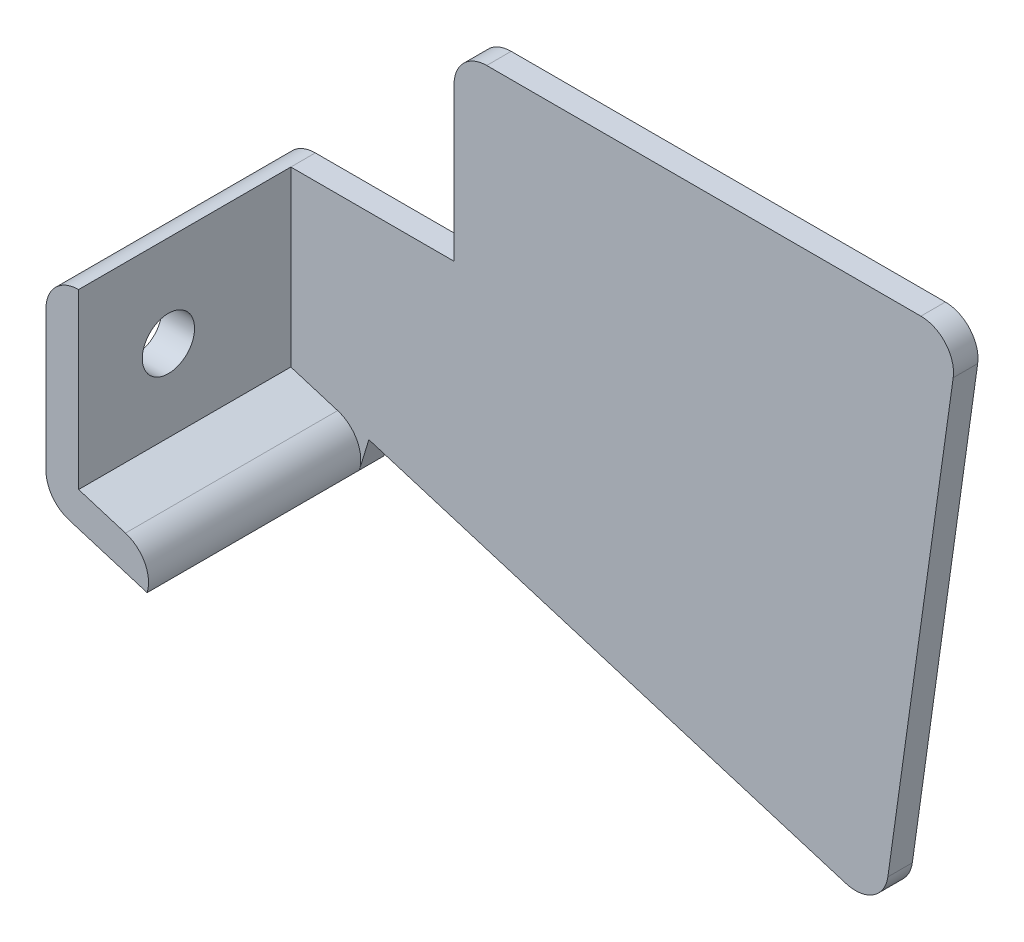
SolidWorks part; units mm, degrees
material "POLYURETHANE (11671)"
ref_plane "Front Plane" through (0, 0, 0) normal (0, 0, 1) x (1, 0, 0)
ref_plane "Top Plane" through (0, 0, 0) normal (0, 1, 0) x (1, 0, 0)
ref_plane "Right Plane" through (0, 0, 0) normal (1, 0, 0) x (0, 0, -1)
sketch "Sketch1" plane through (0, 0, 0) normal (0, 0, 1) x (1, 0, 0)
  line L5 (-6.1742, -3.4117) -> (24.7275, -3.4117)
  line L9 (20.078, -36.4952) -> (24.7275, -3.4117)
  line L16 (-18.1742, -24.8003) -> (20.078, -36.4952)
  line L17 (-18.1742, -14.8003) -> (-18.1742, -24.8003)
  line L21 (-18.1742, -14.8003) -> (-6.1742, -14.8003)
  line L22 (-6.1742, -3.4117) -> (-6.1742, -14.8003)
  dimension "D1" = 107
  dimension "D4" = 82
  dimension "D2" = 40
  dimension "D3" = 12
  dimension "D5" = 10
extrude "Boss-Extrude1" add sketch "Sketch1" along normal blind 1.5
sketch "Sketch6" plane through (0, 0, 0) normal (0, 0, -1) x (-1, 0, 0)
  line L0 (16.1742, -25.4118) -> (11.3927, -26.8736)
  line L1 (18.1742, -14.8003) -> (16.1742, -14.8003)
  line L2 (18.1742, -14.8003) -> (18.1742, -26.8917)
  line L4 (16.1742, -14.8003) -> (16.1742, -25.4118)
  line L5 (11.3927, -26.8736) -> (11.9774, -28.7862)
  line L6 (11.9774, -28.7862) -> (18.1742, -26.8917)
  line L7 (18.1742, -24.8003) -> (-20.078, -36.4952) construction
  dimension "D1" = 2
  dimension "D2" = 2
  dimension "D3" = 5
extrude "Boss-Extrude4" add sketch "Sketch6" against normal blind 14.5
fillet "Fillet3" radius 2 6 edges at (-18.1742, -26.8917, 7.25) (20.078, -36.4952, 0.75) (-6.1742, -3.4117, 0.75) (24.7275, -3.4117, 0.75) (-11.3927, -26.8736, 8) (-18.1742, -14.8003, 7.25)
sketch "Sketch7" plane through (-16.1742, 0, 0) normal (1, 0, 0) x (0, 0, -1)
  line L0 (-1.5, -14.8003) -> (-1.5, -25.4118) construction
  line L1 (-14.5, -25.4118) -> (-1.5, -25.4118) construction
  circle A0 centre (-9, -20.4118) radius 1.6
  dimension "D1" = 3.2
  dimension "D2" = 7.5
  dimension "D3" = 5
extrude "Cut-Extrude1" cut sketch "Sketch7" against normal up to next
